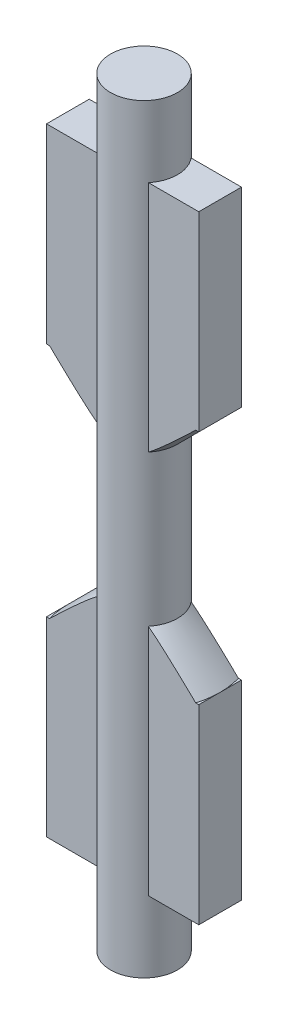
SolidWorks part; units mm, degrees
ref_plane "Front Plane" through (0, 0, 0) normal (0, 0, 1) x (1, 0, 0)
ref_plane "Top Plane" through (0, 0, 0) normal (0, 1, 0) x (1, 0, 0)
ref_plane "Right Plane" through (0, 0, 0) normal (1, 0, 0) x (0, 0, -1)
sketch "Sketch1" plane through (0, 0, 0) normal (0, 1, 0) x (1, 0, 0)
  circle A0 centre (0, 0) radius 2.35
  dimension "D1" = 4.7
extrude "Boss-Extrude1" add sketch "Sketch1" along normal blind 5
sketch "Sketch2" plane through (0, 5, 0) normal (0, 1, 0) x (1, 0, 0)
  line L0 (-1.809, -1.5) -> (-5.35, -1.5)
  line L1 (-5.35, -1.5) -> (-5.35, 1.5)
  line L2 (-5.35, 1.5) -> (-1.809, 1.5)
  line L3 (0, 2.35) -> (0, -2.35) construction
  line L4 (0, 0) -> (-2.35, 0) construction
  line L5 (-2.35, 0) -> (-5.35, 0) construction
  line L6 (5.35, 1.5) -> (1.809, 1.5)
  line L7 (5.35, -1.5) -> (5.35, 1.5)
  line L8 (1.809, -1.5) -> (5.35, -1.5)
  arc A0 (-2.35, 0) -> (-1.809, -1.5) centre (0, 0) ccw construction
  circle A1 centre (0, 0) radius 2.35
  arc A2 (-1.809, -1.5) -> (1.809, -1.5) centre (0, 0) ccw
  arc A3 (-1.809, 1.5) -> (-2.35, 0) centre (0, 0) ccw construction
  arc A4 (1.809, 1.5) -> (-1.809, 1.5) centre (0, 0) ccw
  arc A5 (1.809, -1.5) -> (1.809, 1.5) centre (0, 0) ccw construction
  point P10 (0, 0)
  dimension "D2" = 3
  dimension "D3" = 3
  dimension "D1" = 0
extrude "Boss-Extrude2" add sketch "Sketch2" along normal blind 13.4
extrude "Boss-Extrude3" add sketch "Sketch1<2>" along normal blind 16.6 from surface starting at face at (0, 18.4, 0)
sketch "Sketch1<2>" plane through (0, 0, 0) normal (0, 1, 0) x (1, 0, 0) same geometry as "Sketch1"
extrude "Boss-Extrude4" add sketch "Sketch2<2>" along normal blind 13.4 from surface starting at face at (0, 35, 2.35)
sketch "Sketch2<2>" plane through (0, 5, 0) normal (0, 1, 0) x (1, 0, 0) same geometry as "Sketch2"
extrude "Boss-Extrude5" add sketch "Sketch1<3>" along normal blind 5 from surface starting at face at (0, 48.4, 0)
sketch "Sketch1<3>" plane through (0, 0, 0) normal (0, 1, 0) x (1, 0, 0) same geometry as "Sketch1"
chamfer "Chamfer1" distance 3 angle 45 4 edges at (-2.35, 35, 0) (2.35, 35, 0) (2.35, 18.4, 0) (-2.35, 18.4, 0)
